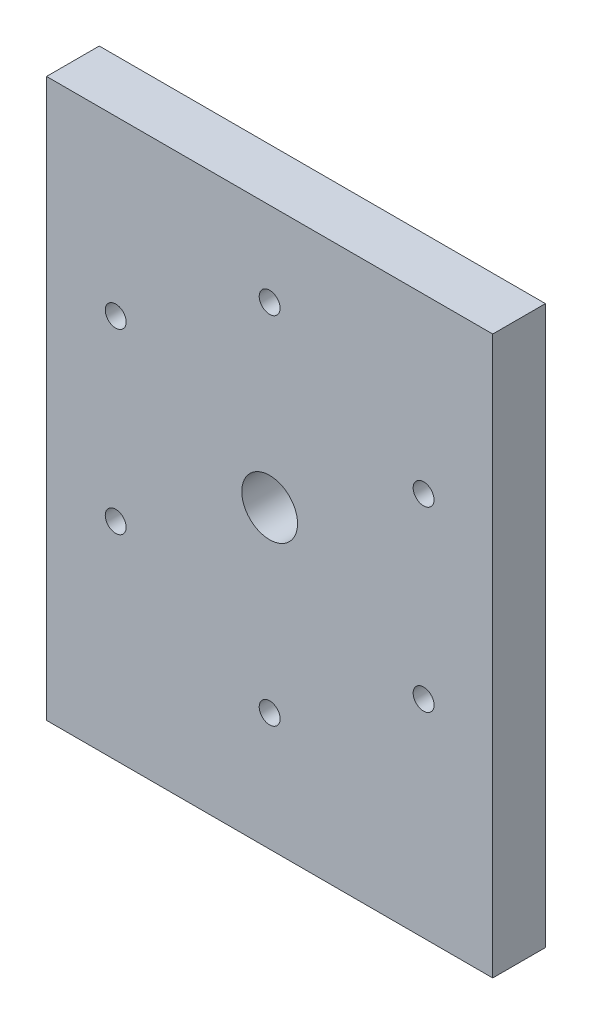
SolidWorks part; units mm, degrees
material "Acrylic (Medium-high impact)"
ref_plane "Front Plane" through (0, 0, 0) normal (0, 0, 1) x (1, 0, 0)
ref_plane "Top Plane" through (0, 0, 0) normal (0, 1, 0) x (1, 0, 0)
ref_plane "Right Plane" through (0, 0, 0) normal (1, 0, 0) x (0, 0, -1)
sketch "Sketch1" plane through (0, 0, 0) normal (0, 0, 1) x (1, 0, 0)
  line L0 (34.1802, 50.5429) -> (34.1802, 53.0508) construction
  line L1 (-50.8, 127) -> (50.8, 127)
  line L2 (-50.8, 127) -> (-50.8, 0)
  line L3 (-50.8, 0) -> (50.8, 0)
  line L4 (50.8, 127) -> (50.8, 0)
  circle A0 centre (0, 67.375) radius 6.35
  circle A7 centre (0, 67.375) radius 38.1 construction
  dimension "D1" = 127
  dimension "D3" = 12.7
  dimension "D12" = 76.2
  dimension "D2" = 101.6
  dimension "D5" = 67.375
extrude "Boss-Extrude1" add sketch "Sketch1" along normal blind 12
sketch "Sketch2" plane through (0, 0, 0) normal (0, 0, -1) x (-1, 0, 0)
  circle A0 centre (0, 107.8562) radius 2.3812
  circle A1 centre (0, 67.375) radius 38.1 construction
  dimension "D1" = 4.7625
extrude "Cut-Extrude1" cut sketch "Sketch2" against normal through all
pattern_circular "CirPattern1" count 6 every 60 about axis through (0, 67.375, 12) along (0, 0, -1) of "Cut-Extrude1"
sketch "Sketch3" plane through (0, 0, 0) normal (0, -1, 0) x (1, 0, 0)
  line L0 (31.75, 6) -> (-31.75, 6) construction
  line L2 (0, 0) -> (0, 12) construction
  line L3 (-50.8, 12) -> (50.8, 12) construction
  circle A0 centre (31.75, 6) radius 1.27
  circle A1 centre (0, 6) radius 1.27
  circle A2 centre (-31.75, 6) radius 1.27
  point P4 (0, 0)
  point P6 (0, 0)
  point P8 (0, 0)
  point P9 (0, 6)
  point P10 (0, 0)
  dimension "D2" = 2.54
  dimension "D1" = 31.75
extrude "Cut-Extrude2" cut sketch "Sketch3" against normal blind 12.7
hole_wizard "#10-32 Tapped Hole3" positions "Sketch11" profile "Sketch13" tap size "#10-32" standard "ANSI Inch"
sketch "Sketch11" plane through (0, 0, 0) normal (0, -1, 0) x (-1, 0, 0)
  point P0 (-31.75, -6)
  point P3 (0, -6)
  point P6 (31.75, -6)
sketch "Sketch13" plane through (31.75, 0, 6) normal (1, 0, 0) x (0, 0, -1)
  line L0 (0, 0) -> (0, 13.9133)
  line L1 (0, 13.9133) -> (2.0193, 12.7)
  line L2 (2.0193, 12.7) -> (2.0193, 0)
  line L5 (2.0193, 0) -> (0, 0)
  line L10 (0, 13.9133) -> (-2.0193, 12.7) construction
  line L11 (0, -6.35) -> (0, 107.95) construction
  dimension "Tap Drill Dia." = 4.0386
  dimension "Tap Drill Depth" = 12.7
  dimension "Drill Angle" = 118
cosmetic thread "Hole Thread10" parameters "D1"=10.16, "D2"=4.826
cosmetic thread "Hole Thread11" parameters "D1"=10.16, "D2"=4.826
cosmetic thread "Hole Thread12" parameters "D1"=10.16, "D2"=4.826
